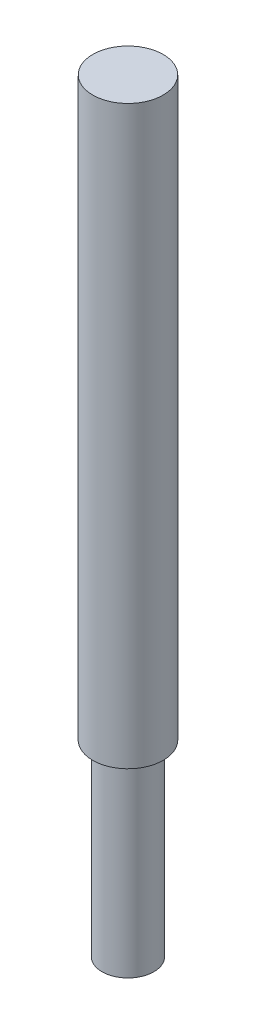
SolidWorks part; units mm, degrees
material "6061 Alloy"
ref_plane "Front Plane" through (0, 0, 0) normal (0, 0, 1) x (1, 0, 0)
ref_plane "Top Plane" through (0, 0, 0) normal (0, 1, 0) x (1, 0, 0)
ref_plane "Right Plane" through (0, 0, 0) normal (1, 0, 0) x (0, 0, -1)
sketch "Sketch1" plane through (0, 0, 0) normal (0, 1, 0) x (1, 0, 0)
  circle A0 centre (0, 0) radius 2.3813
  dimension "D1" = 4.7625
extrude "Boss-Extrude1" add sketch "Sketch1" along normal blind 38.9763
sketch "Sketch2" plane through (0, 0, 0) normal (0, -1, 0) x (1, 0, 0)
  circle A0 centre (0, 0) radius 1.7526
  dimension "D1" = 3.5052
extrude "Boss-Extrude2" add sketch "Sketch2" along normal blind 12.7
